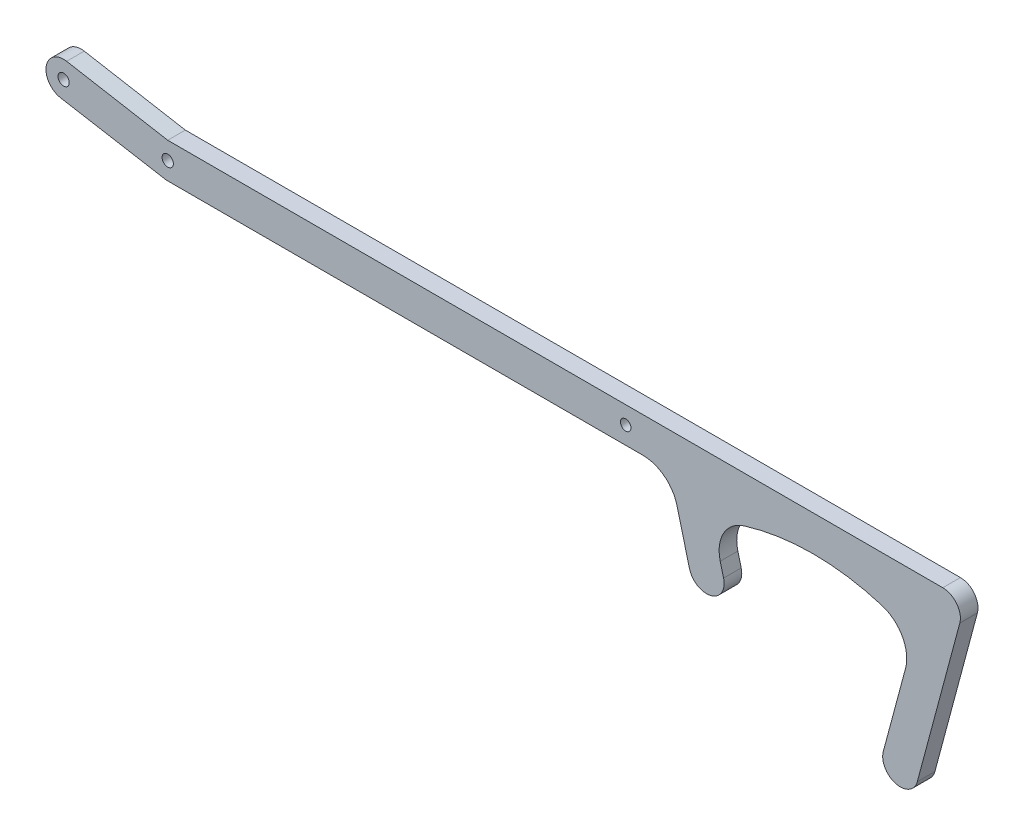
SolidWorks part; units mm, degrees
ref_plane "Front Plane" through (0, 0, 0) normal (0, 0, 1) x (1, 0, 0)
ref_plane "Top Plane" through (0, 0, 0) normal (0, 1, 0) x (1, 0, 0)
ref_plane "Right Plane" through (0, 0, 0) normal (1, 0, 0) x (0, 0, -1)
sketch "Sketch1" plane through (0, 0, 0) normal (0, 0, 1) x (1, 0, 0)
  line L0 (0, 0) -> (279.4, 0) construction
  line L1 (0, 6.35) -> (279.4, 6.35)
  line L2 (0, -6.35) -> (181.1202, -6.35)
  line L3 (285.5336, -1.6435) -> (270.2203, -58.7935)
  line L4 (257.9531, -55.5065) -> (268.9126, -14.605)
  line L6 (188.0883, -33.3375) -> (181.1202, -6.35)
  line L7 (200.3851, -30.1625) -> (196.3681, -14.605)
  line L8 (0, 0) -> (-37.5378, 6.521) construction
  line L10 (0, 6.35) -> (-36.4351, 12.7745)
  line L11 (-38.6246, 0.2647) -> (-1.0868, -6.2563)
  circle A0 centre (0, 0) radius 2.032
  arc A2 (285.5336, -1.6435) -> (279.4, 6.35) centre (279.4, 0) ccw
  arc A3 (257.9531, -55.5065) -> (270.2203, -58.7935) centre (264.0867, -57.15) ccw
  arc A5 (188.0883, -33.3375) -> (200.3851, -30.1625) centre (194.2367, -31.75) ccw
  arc A6 (196.3681, -14.605) -> (268.9126, -14.605) centre (232.6404, -90.8741) cw
  circle A7 centre (165.1, 0) radius 1.905
  arc A9 (-36.4351, 12.7745) -> (-38.6246, 0.2647) centre (-37.5378, 6.521) ccw
  circle A10 centre (-37.5378, 6.521) radius 2.032
  arc A12 (0, -6.35) -> (-1.0868, -6.2563) centre (0, 0) cw
  dimension "D1" = 31.75
  dimension "D3" = 6.35
  dimension "D5" = 6.35
  dimension "D6" = 6.35
  dimension "D11" = 4.064
  dimension "D14" = 17.145
  dimension "D10" = 75
  dimension "D13" = 84.455
  dimension "D15" = 3.81
  dimension "D19" = 6.35
  dimension "D21" = 4.064
  dimension "D17" = 6.35
  dimension "D4" = 12.7
  dimension "D7" = 279.4
  dimension "D8" = 57.15
  dimension "D9" = 69.85
  dimension "D12" = 26.9875
  dimension "D16" = 165.1
  dimension "D18" = 38.1
  dimension "D20" = 170
extrude "Boss-Extrude1" add sketch "Sketch1" along normal mid plane 6.35
fillet "Fillet1" radius 12.7 1 edges at (181.1202, -6.35, 0)
fillet "Fillet2" radius 12.7 2 edges at (268.9126, -14.605, 0) (196.3681, -14.605, 0)
